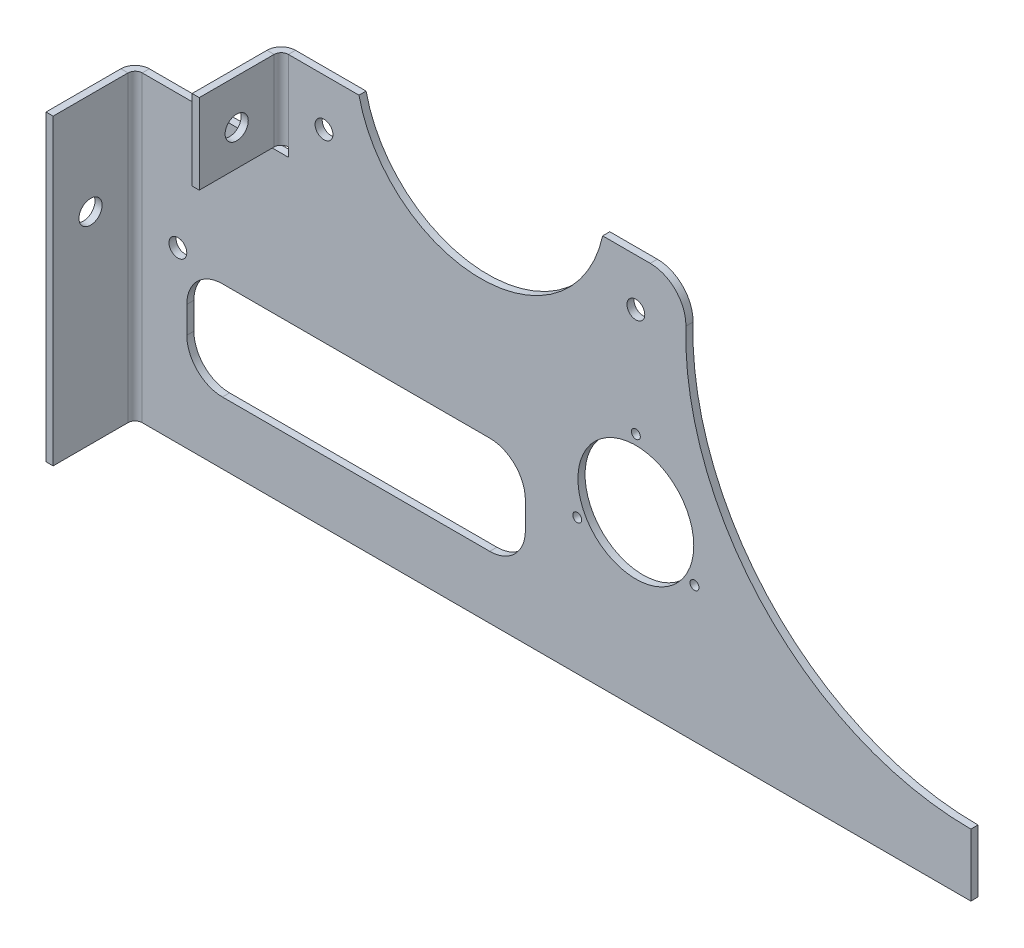
SolidWorks part; units mm, degrees
note: The reader was unsure of these and kept them because the rebuilt part matched: thickness of "基体-法兰1", "边线-法兰1", "钣金6", "钣金7", "钣金8", "钣金10", "钣金11"; flange length of "边线-法兰1".
material "Q355"
ref_plane "前视基准面" through (0, 0, 0) normal (0, 0, 1) x (1, 0, 0)
ref_plane "上视基准面" through (0, 0, 0) normal (0, 1, 0) x (1, 0, 0)
ref_plane "右视基准面" through (0, 0, 0) normal (1, 0, 0) x (0, 0, -1)
sketch "草图1" plane through (0, 0, 0) normal (0, 0, 1) x (1, 0, 0)
  line L0 (0, 0) -> (0, 170)
  line L1 (0, 170) -> (82, 170)
  line L2 (82, 170) -> (82, 220)
  line L5 (82, 220) -> (121.626, 220)
  line L6 (258.374, 220) -> (306.9652, 220)
  line L7 (0, 0) -> (465, 0)
  line L8 (465, 0) -> (465, 35)
  line L9 (465, 35) -> (465, 195) construction
  line L11 (25, 90) -> (215, 90)
  line L12 (25, 90) -> (25, 35)
  line L13 (25, 35) -> (215, 35)
  line L14 (215, 90) -> (215, 35)
  arc A0 (121.626, 220) -> (258.374, 220) centre (190, 235) ccw
  arc A1 (306.9652, 220) -> (465, 35) centre (465, 195) ccw
  dimension "D6" = 15
  dimension "D10" = 160
  dimension "D13" = 25
  dimension "D3" = 70
  dimension "D5" = 190
  dimension "D1" = 170
  dimension "D2" = 82
  dimension "D4" = 220
  dimension "D9" = 465
  dimension "D11" = 195
  dimension "D12" = 35
  dimension "D14" = 190
  dimension "D15" = 55
base flange "基体-法兰1" sketch "草图1" thickness 4 reverse thickness direction no parameters "D1"=4
sketch "草图6" plane through (0, 0, 0) normal (0, 0, 1) x (1, 0, 0)
  line L0 (0, 0) -> (465, 0) construction
  line L1 (465, 0) -> (465, 35) construction
  line L2 (277, 95) -> (277, 140.8548) construction
  line L3 (277, 140.8548) -> (277, 95) construction
  line L4 (277, 95) -> (265.3415, 88.269) construction
  line L5 (277, 95) -> (363.8682, 44.8467) construction
  circle A0 centre (277, 95) radius 32.5
  circle A1 centre (277, 95) radius 38 construction
  circle A3 centre (277, 133) radius 2.5
  circle A4 centre (309.909, 76) radius 2.5
  circle A5 centre (244.091, 76) radius 2.5
  dimension "D1" = 65
  dimension "D4" = 76
  dimension "D7" = 5
  dimension "D8" = 5
  dimension "D9" = 5
  dimension "D2" = 95
  dimension "D3" = 188
  dimension "D5" = 120
  dimension "D6" = 120
extrude "切除-拉伸1" cut sketch "草图6" against normal blind 10 normal cut yes
sketch "草图7" plane through (0, 0, 0) normal (0, 0, 1) x (1, 0, 0)
  line L0 (0, 0) -> (465, 0) construction
  line L1 (0, 170) -> (0, 0) construction
  line L3 (82, 220) -> (82, 170) construction
  circle A0 centre (20, 95) radius 5
  circle A1 centre (102, 193.5) radius 5
  circle A2 centre (277, 193.5) radius 5
  dimension "D1" = 10
  dimension "D2" = 10
  dimension "D6" = 20
  dimension "D7" = 175
  dimension "D3" = 95
  dimension "D4" = 20
  dimension "D5" = 98.5
extrude "切除-拉伸2" cut sketch "草图7" against normal blind 10 normal cut yes
fillet "圆角1" radius 20 4 edges at (25, 35, -2) (25, 90, -2) (215, 35, -2) (215, 90, -2)
fillet "圆角2" radius 20 1 edges at (306.9652, 220, -2)
edge flange "边线-法兰1" sketch "草图13" flange profiles "草图13", "草图14" flange angle 90 flange length 50 flange position bend outside bend radius 4 thickness 4 relief rectangular parameters "D6"=10, "D8"=1
sketch "草图13" plane through (82, 0, 0) normal (-1, 0, 0) x (0, -1, 0)
  line L0 (-220, 0) -> (-170, 0) construction
  line L1 (-220, 0) -> (-175, 0)
  line L2 (-220, 0) -> (-220, 46)
  line L3 (-220, 46) -> (-175, 46)
  line L4 (-175, 46) -> (-175, 0)
  dimension "D1" = 45
sketch "草图14" plane through (0, 0, 0) normal (-1, 0, 0) x (0, -1, 0)
  line L0 (-170, 0) -> (0, 0) construction
  line L1 (-170, 0) -> (0, 0)
  line L2 (-170, 0) -> (-170, 46)
  line L3 (-170, 46) -> (0, 46)
  line L4 (0, 46) -> (0, 0)
bend "边线折弯1" bend radius 4 bend angle 90 parameters "D5"=1
bend "边线折弯2" bend radius 4 bend angle 90 parameters "D5"=2
sketch "草图15" plane through (-8, 0, 0) normal (-1, 0, 0) x (0, 0, 1)
  line L0 (46, 220) -> (4, 220) construction
  line L1 (-4, 220) -> (-4, 175) construction
  circle A0 centre (25, 113) radius 6.5
  circle A1 centre (25, 195) radius 6.5
  dimension "D1" = 82
  dimension "D2" = 25
  dimension "D3" = 13
  dimension "D4" = 29
extrude "切除-拉伸4" cut sketch "草图15" against normal up to next
sketch "折弯-线1" [suppressed] plane through (0, 0, 0) normal (0, 1, 0) x (1, 0, 0)
sketch "边界框1" [suppressed] plane through (0, 0, 0) normal (0, 1, 0) x (1, 0, 0)
sheet metal parameters "钣金6" thickness 4 parameters "D1"=4
flat pattern "平板型式6" [suppressed]
sketch "折弯-线2" plane through (0, 0, 0) normal (0, 1, 0) x (1, 0, 0)
sketch "边界框2" [suppressed] plane through (0, 0, 0) normal (0, 1, 0) x (1, 0, 0)
sheet metal parameters "钣金7" thickness 4 parameters "D1"=4, "D7"=5
flat pattern "平板型式6"
sketch "折弯-线2" plane through (0, 0, 0) normal (0, 1, 0) x (1, 0, 0)
sketch "边界框2" [suppressed] plane through (0, 0, 0) normal (0, 1, 0) x (1, 0, 0)
sheet metal parameters "钣金8" thickness 4 parameters "D1"=4, "D7"=5
flat pattern "平板型式6"
sketch "折弯-线2" plane through (0, 0, 0) normal (0, 1, 0) x (1, 0, 0)
sketch "边界框2" [suppressed] plane through (0, 0, 0) normal (0, 1, 0) x (1, 0, 0)
sheet metal parameters "钣金10" thickness 4 parameters "D1"=4, "D7"=5
flat pattern "平板型式6" [suppressed]
sketch "折弯-线2" plane through (0, 0, 0) normal (0, 0, 1) x (1, 0, 0)
  line L0 (45.9159, 150) -> (45.9159, 0) construction
  line L1 (127.4159, 206) -> (127.4159, 155) construction
  line L2 (45.9159, 150) -> (45.9159, 0) construction
  line L3 (127.4159, 206) -> (127.4159, 155) construction
sketch3d "边界框2" [suppressed]
  line L0 (-514.5, 24, 0) -> (0, 24, 0) construction
  line L1 (-514.5, -182, 0) -> (0, -182, 0) construction
  line L2 (-514.5, 24, 0) -> (-514.5, -182, 0) construction
  line L3 (0, 24, 0) -> (0, -182, 0) construction
bend of the flat pattern "展开-<边线折弯1>1"
bend of the flat pattern "展开-<边线折弯2>1"
sheet metal parameters "钣金11" thickness 4 parameters "D1"=4, "D7"=5
flat pattern "平板型式6"
sketch "折弯-线2" plane through (0, 0, 0) normal (0, 0, 1) x (1, 0, 0)
  line L4 (-4.7124, 170) -> (-4.7124, 0) construction
  line L5 (77.2876, 220) -> (77.2876, 175) construction
  line L6 (-4.7124, 170) -> (-4.7124, 0) construction
  line L7 (77.2876, 220) -> (77.2876, 175) construction
  point P0 (45.9159, 150)
  point P1 (45.9159, 0)
  point P2 (127.4159, 206)
  point P3 (127.4159, 155)
sketch3d "边界框2" [suppressed]
  line L0 (-516.4248, 25, 0) -> (0, 25, 0) construction
  line L1 (-516.4248, -195, 0) -> (0, -195, 0) construction
  line L2 (-516.4248, 25, 0) -> (-516.4248, -195, 0) construction
  line L3 (0, 25, 0) -> (0, -195, 0) construction
bend of the flat pattern "展开-<边线折弯1>1"
bend of the flat pattern "展开-<边线折弯2>1"
